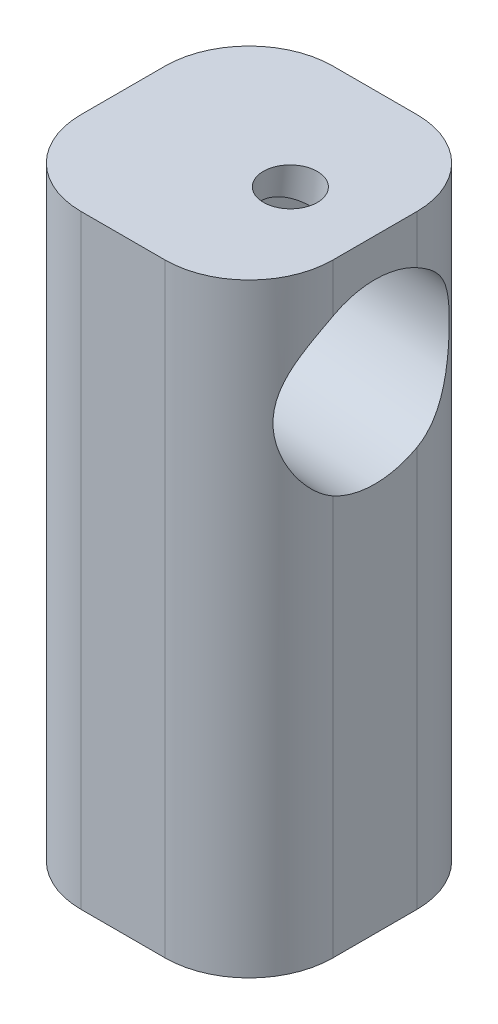
SolidWorks part; units mm, degrees
ref_plane "Front Plane" through (0, 0, 0) normal (0, 0, 1) x (1, 0, 0)
ref_plane "Top Plane" through (0, 0, 0) normal (0, 1, 0) x (1, 0, 0)
ref_plane "Right Plane" through (0, 0, 0) normal (1, 0, 0) x (0, 0, -1)
sketch "Sketch1" plane through (0, 0, 0) normal (0, 1, 0) x (1, 0, 0)
  line L1 (7.5, -7.5) -> (-7.5, -7.5)
  line L2 (7.5, -7.5) -> (7.5, 7.5)
  line L3 (7.5, 7.5) -> (-7.5, 7.5)
  line L4 (-7.5, -7.5) -> (-7.5, 7.5)
  line L5 (7.5, -7.5) -> (-7.5, 7.5) construction
  line L6 (7.5, 7.5) -> (-7.5, -7.5) construction
  circle A0 centre (0, 0) radius 4.15
  point P0 (0, 0)
  dimension "D1" = 8.3
  dimension "D2" = 15
extrude "Boss-Extrude1" add sketch "Sketch1" along normal blind 20
sketch "Sketch2" plane through (0, 20, 0) normal (0, 1, 0) x (1, 0, 0)
  line L1 (-7.5, -7.5) -> (7.5, -7.5)
  line L2 (-7.5, -7.5) -> (-7.5, 7.5)
  line L3 (-7.5, 7.5) -> (7.5, 7.5)
  line L4 (7.5, -7.5) -> (7.5, 7.5)
  line L5 (-7.5, -7.5) -> (7.5, 7.5) construction
  line L6 (-7.5, 7.5) -> (7.5, -7.5) construction
  point P0 (0, 0)
extrude "Boss-Extrude2" add sketch "Sketch2" along normal blind 16
fillet "Fillet1" radius 5 4 edges at (-7.5, 18, -7.5) (7.5, 18, -7.5) (-7.5, 18, 7.5) (7.5, 18, 7.5)
ref_plane "Plane1" through (3.9965, -0.3848, 0) normal (0.9954, -0.0958, 0) x (0, 0, -1)
ref_plane "Plane2" through (3.5035, 36.3848, 0) normal (-0.0958, -0.9954, 0) x (0, 0, -1)
sketch "Sketch3" plane through (4.0461, 0.1295, 0) normal (0.9954, -0.0958, 0) x (0, 0, -1)
  line L0 (-2.5, 36.0364) -> (2.5, 36.0364) construction
  circle A0 centre (0, 28.5364) radius 2.5
  dimension "D2" = 5
  dimension "D1" = 7.5
extrude "Cut-Extrude1" cut sketch "Sketch3" against normal through all and the other way through all
sketch "Sketch4" plane through (4.0461, 0.1295, 0) normal (0.9954, -0.0958, 0) x (0, 0, -1)
  circle A0 centre (0, 28.5364) radius 5.25
  dimension "D1" = 10.5
extrude "Cut-Extrude2" cut sketch "Sketch4" against normal blind 7 and the other way through all
sketch "Sketch5" plane through (15.2828, 35.2506, 0) normal (-0.0958, -0.9954, 0) x (-0.9954, 0.0958, 0)
  circle A0 centre (12.8339, 0) radius 1.6
  dimension "D2" = 3.2
  dimension "D1" = 1
extrude "Cut-Extrude3" cut sketch "Sketch5" along normal up to next and the other way blind 10
chamfer "Chamfer1" distance 10 angle 1 1 edges at (0, 20, 4.15) first distance on face at (0, 20, 4.15)
